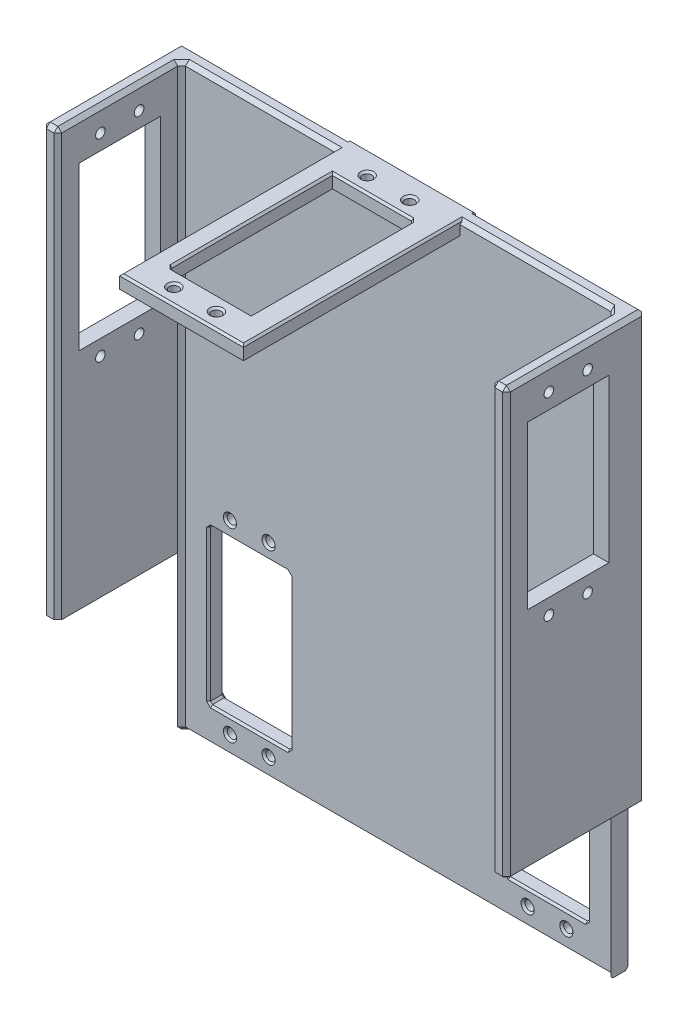
SolidWorks part; units mm, degrees
material "ABS"
ref_plane "Front Plane" through (0, 0, 0) normal (0, 0, 1) x (1, 0, 0)
ref_plane "Top Plane" through (0, 0, 0) normal (0, 1, 0) x (1, 0, 0)
ref_plane "Right Plane" through (0, 0, 0) normal (1, 0, 0) x (0, 0, -1)
sketch "Sketch1" plane through (0, 0, 0) normal (0, 0, 1) x (1, 0, 0)
  line L1 (-60, 75) -> (60, 75)
  line L2 (-60, 75) -> (-60, -75)
  line L3 (-60, -75) -> (60, -75)
  line L4 (60, 75) -> (60, -75)
  line L5 (-60, 75) -> (60, -75) construction
  line L6 (-60, -75) -> (60, 75) construction
  point P0 (0, 0)
  dimension "D1" = 150
  dimension "D2" = 120
extrude "Boss-Extrude1" add sketch "Sketch1" along normal blind 4
ref_plane "Plane1" through (0, 0, 0) normal (1, 0, 0) x (0, 0, -1)
sketch "Sketch2" plane through (60, 0, 0) normal (1, 0, 0) x (0, 0, -1)
  line L0 (-4, -75) -> (0, -75) construction
  line L1 (-4, 75) -> (-36, 75)
  line L2 (-4, 75) -> (-4, -75)
  line L3 (-4, -75) -> (-36, -75)
  line L4 (-36, 75) -> (-36, -75)
  dimension "D1" = 32
extrude "Boss-Extrude2" add sketch "Sketch2" against normal blind 4
mirror "Mirror1" about plane through (0, 0, 0) normal (1, 0, 0) of "Boss-Extrude2"
sketch "Sketch3" plane through (60, 0, 0) normal (1, 0, 0) x (0, 0, -1)
  line L0 (-36, 75) -> (-36, -75) construction
  line L1 (-30.5, 65) -> (-9.5, 65)
  line L2 (-30.5, 65) -> (-30.5, 23)
  line L3 (-30.5, 23) -> (-9.5, 23)
  line L4 (-9.5, 65) -> (-9.5, 23)
  line L5 (-36, 75) -> (0, 75) construction
  circle A0 centre (-25, 69) radius 1.25
  circle A1 centre (-15, 69) radius 1.25
  circle A2 centre (-25, 19) radius 1.25
  circle A3 centre (-15, 19) radius 1.25
  dimension "D9" = 2.5
  dimension "D1" = 42
  dimension "D2" = 21
  dimension "D3" = 5.5
  dimension "D4" = 10
  dimension "D5" = 4
  dimension "D6" = 4
  dimension "D7" = 10
  dimension "D8" = 5.5
extrude "Cut-Extrude1" cut sketch "Sketch3" against normal through all both and the other way through all
chamfer "Chamfer1" distance 1 angle 45 4 edges at (60, 0, 0) (0, 75, 0) (0, -75, 0) (-60, 0, 0)
chamfer "Chamfer2" distance 1 angle 45 20 edges at (-58, 75, 36) (-56, 0, 36) (58, 75, 36) (56, 0, 36) (60, 75, 18.5) (60, 0, 36) (60, -75, 18.5) (58, -75, 36) (56, 75, 20) (-56, 75, 20) (-56, 0, 4) (0, 75, 4) (56, 0, 4) (56, -75, 20) (0, -75, 4) (-56, -75, 20) (-58, -75, 36) (-60, -75, 18.5) (-60, 0, 36) (-60, 75, 18.5)
sketch "Sketch4" plane through (0, 0, 4) normal (0, 0, 1) x (1, 0, 0)
  line L0 (0, -88.8044) -> (0, 88.8044) construction
  line L1 (28, -66) -> (49, -66)
  line L2 (28, -66) -> (28, -26)
  line L3 (28, -26) -> (49, -26)
  line L4 (49, -66) -> (49, -26)
  line L5 (-55, -74) -> (55, -74) construction
  circle A0 centre (43.5, -70) radius 1.2
  circle A1 centre (33.5, -70) radius 1.2
  circle A2 centre (33.5, -22) radius 1.2
  circle A3 centre (43.5, -22) radius 1.2
  dimension "D5" = 2.4
  dimension "D1" = 21
  dimension "D2" = 40
  dimension "D3" = 28
  dimension "D4" = 8
  dimension "D6" = 5.5
  dimension "D7" = 4
  dimension "D8" = 4
  dimension "D9" = 5.5
extrude "Cut-Extrude2" cut sketch "Sketch4" against normal blind 10
chamfer "Chamfer3" distance 0.5 angle 45 20 edges at (44.7, -22, 4) (44.7, -22, 0) (34.7, -22, 4) (34.7, -22, 0) (34.7, -70, 4) (34.7, -70, 0) (44.7, -70, 4) (44.7, -70, 0) (38.5, -26, 4) (28, -46, 4) (28, -26, 2) (49, -26, 2) (28, -66, 2) (38.5, -66, 4) (49, -46, 4) (49, -66, 2) (38.5, -66, 0) (49, -46, 0) (38.5, -26, 0) (28, -46, 0)
mirror "Mirror2" about plane through (0, 0, 0) normal (1, 0, 0) of "Chamfer3", "Cut-Extrude2"
sketch "Sketch5" plane through (60, 0, 0) normal (1, 0, 0) x (0, 0, -1)
  line L0 (-36, -74) -> (-36, 74) construction
  line L1 (-36, -35) -> (0, -35)
  line L2 (-36, -35) -> (-36, -75)
  line L3 (-36, -75) -> (0, -75)
  line L4 (0, -35) -> (0, -75)
  line L5 (-1, -75) -> (-35, -75) construction
  line L6 (0, 74) -> (0, -74) construction
  dimension "D1" = 40
extrude "Cut-Extrude3" cut sketch "Sketch5" against normal blind 4
chamfer "Chamfer4" distance 0.5 angle 45 10 edges at (56, -35, 20) (56.5, -35, 35.5) (58, -35, 36) (59.5, -35, 35.5) (60, -35, 18) (59.5, -35, 0.5) (57.5, -35, 0) (56, -54.5, 0) (56, -74.5, 0.5) (56, -75, 2.5)
mirror "Mirror3" about plane through (0, 0, 0) normal (1, 0, 0) of "Cut-Extrude3"
sketch "Sketch7" plane through (0, 75, 0) normal (0, 1, 0) x (1, 0, 0)
  line L0 (-59, 0) -> (59, 0) construction
  line L1 (-16, 0) -> (16, 0)
  line L2 (-16, 0) -> (-16, -60)
  line L3 (-16, -60) -> (16, -60)
  line L4 (16, 0) -> (16, -60)
  dimension "D1" = 60
  dimension "D2" = 32
  dimension "D3" = 16
extrude "Boss-Extrude3" add sketch "Sketch7" against normal blind 4
sketch "Sketch8" plane through (0, 75, 0) normal (0, 1, 0) x (1, 0, 0)
  line L0 (-16, -3) -> (-16, -60) construction
  line L1 (-11, -10) -> (10, -10)
  line L2 (-11, -10) -> (-11, -52)
  line L3 (-11, -52) -> (10, -52)
  line L4 (10, -10) -> (10, -52)
  line L5 (-11, -10) -> (10, -52) construction
  line L6 (-11, -52) -> (10, -10) construction
  line L7 (16, 0) -> (-16, 0) construction
  circle A0 centre (-6, -6) radius 1.2
  circle A1 centre (5, -6) radius 1.2
  circle A2 centre (-6, -56) radius 1.2
  circle A3 centre (5, -56) radius 1.2
  point P0 (-0.5, -31)
  dimension "D5" = 2.4
  dimension "D1" = 42
  dimension "D2" = 21
  dimension "D3" = 5
  dimension "D4" = 10
  dimension "D6" = 5
  dimension "D7" = 4
  dimension "D8" = 5
  dimension "D9" = 4
extrude "Cut-Extrude4" cut sketch "Sketch8" against normal blind 4
chamfer "Chamfer5" distance 0.5 angle 45 23 edges at (5, 75, 7.2) (-6, 75, 7.2) (-6, 71, 57.2) (5, 71, 57.2) (5, 75, 57.2) (-6, 75, 57.2) (16, 71, 32) (0, 71, 60) (-16, 71, 32) (0, 75, 0) (-11, 71, 31) (10, 73, 10) (-0.5, 71, 10) (10, 71, 31) (-0.5, 71, 52) (-11, 73, 52) (-11, 75, 31) (-0.5, 75, 52) (-0.5, 75, 10) (10, 75, 31) (16, 75, 31.5) (0, 75, 60) (-16, 75, 31.5)
chamfer "Chamfer6" distance 1 angle 45 1 edges at (0, 71, 4)
